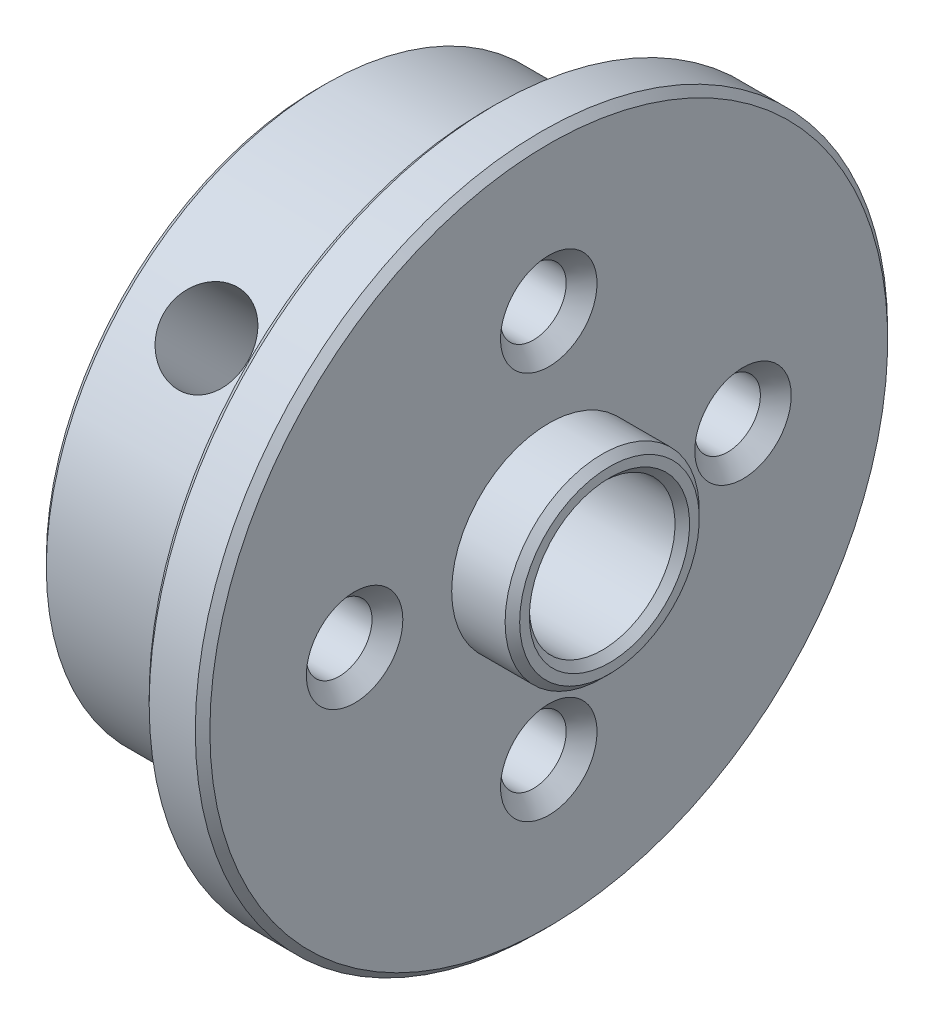
SolidWorks part; units mm, degrees
material "6063-T6, Rod (SS)"
ref_plane "Front" through (0, 0, 0) normal (0, 0, 1) x (1, 0, 0)
ref_plane "Top" through (0, 0, 0) normal (0, 1, 0) x (1, 0, 0)
ref_plane "Right" through (0, 0, 0) normal (1, 0, 0) x (0, 0, -1)
ref_axis "side-side" through (80.9, 0, 0) along (-1, 0, 0)
ref_axis "up-down" through (0, 50, 0) along (0, -1, 0)
ref_axis "front-back" through (0, 0, -80.9) along (0, 0, 1)
sketch "Sketch1" plane through (0, 0, 0) normal (0, 0, 1) x (1, 0, 0)
  line L0 (0, 0) -> (14.0331, 0) construction
  line L1 (-9.5, 3) -> (2.5, 3)
  line L2 (-9.5, 3) -> (-9.5, 11.5)
  line L3 (-2.5, 14.2621) -> (0, 14.2621)
  line L4 (2.5, 3) -> (2.5, 4)
  line L5 (0, -50) -> (0, 50) construction
  line L7 (2.5, 4) -> (0, 4)
  line L8 (0, 14.2621) -> (0, 4)
  line L11 (-9.5, 11.5) -> (-2.5, 11.5)
  line L12 (-2.5, 14.2621) -> (-2.5, 11.5)
  point P13 (14.0331, 0)
  dimension "D1" = 6
  dimension "D2" = 8
  dimension "D3" = 2.5
  dimension "D4" = 2.5
  dimension "D5" = 23
  dimension "D6" = 28.5242
  dimension "D7" = 12
  dimension "D8" = 7
revolve "Revolve1" add sketch "Sketch1" angle 360 about L0
hole_wizard "#6-32 Tapped Hole1" positions "Sketch2" profile "Sketch3" tap size "#6-32" standard "ANSI Inch" end condition through all
sketch "Sketch2" plane through (0, 0, 0) normal (1, 0, 0) x (0, 0, -1)
  circle A0 centre (0, 0) radius 8 construction
  point P4 (0, 8)
  point P6 (0, -8)
  point P8 (8, 0)
  point P10 (-8, 0)
  dimension "D1" = 16
sketch "Sketch3" plane through (0, 0, 8) normal (0, 1, 0) x (0, 0, -1)
  line L0 (0, 0) -> (0, 9.5)
  line L1 (0, 9.5) -> (1.9875, 9.5)
  line L2 (1.3525, 8.865) -> (1.3525, 0.635)
  line L3 (1.3525, 0.635) -> (1.9875, 0)
  line L5 (1.9875, 0) -> (0, 0)
  line L6 (-1.3525, 0.635) -> (-1.9875, 0) construction
  line L7 (1.9875, 9.5) -> (1.3525, 8.865)
  line L8 (-1.9876, 9.5) -> (-1.3526, 8.865) construction
  line L11 (0, -6.35) -> (0, 107.95) construction
  dimension "Thread Major Dia." = 2.7051
  dimension "Thru Tap Drill Depth" = 9.5
  dimension "Near C'Sink Dia." = 3.9751
  dimension "Near C'Sink Angle" = 90
  dimension "Far C'Sink Dia." = 3.9751
  dimension "Far C'Sink Angle" = 90
ref_plane "Plane1" through (0, 0, 0) normal (0, 0.7071, 0.7071) x (-1, 0, 0)
sketch "Sketch4" plane through (0, 0, 0) normal (0, 0.7071, 0.7071) x (-1, 0, 0)
  line L0 (9.5, -11.5) -> (9.5, 11.5) construction
  circle A0 centre (6, 0) radius 1.25
  point P2 (4.3508, 0)
  dimension "D2" = 2.5
  dimension "D1" = 3.5
extrude "Boss-Extrude1" add sketch "Sketch4" along normal blind 1.5 from offset 10
hole_wizard "#8-32 Tapped Hole1" positions "Sketch5" profile "Sketch6" tap size "#8-32" standard "ANSI Inch"
sketch "Sketch5" plane through (0, 8.1317, 8.1317) normal (0, 0.7071, 0.7071) x (1, 0, 0)
  point P0 (-6, 0)
sketch "Sketch6" plane through (-6, 8.1317, 8.1317) normal (1, 0, 0) x (0, -0.7071, 0.7071)
  line L0 (0, 0) -> (0, 11.7458)
  line L1 (0, 11.7458) -> (1.7272, 10.708)
  line L2 (1.7272, 10.708) -> (1.7272, 0)
  line L5 (1.7272, 0) -> (0, 0)
  line L10 (0, 11.7458) -> (-1.7272, 10.708) construction
  line L11 (0, -6.35) -> (0, 107.95) construction
  dimension "Tap Drill Dia." = 3.4544
  dimension "Tap Drill Depth" = 10.708
  dimension "Drill Angle" = 118
chamfer "Chamfer1" distance 0.3 angle 45 6 edges at (-9.5, 0, 11.5) (-2.5, 0, 14.2621) (0, 0, 14.2621) (2.5, 0, 3) (2.5, 0, 4) (-9.5, 0, 3)
